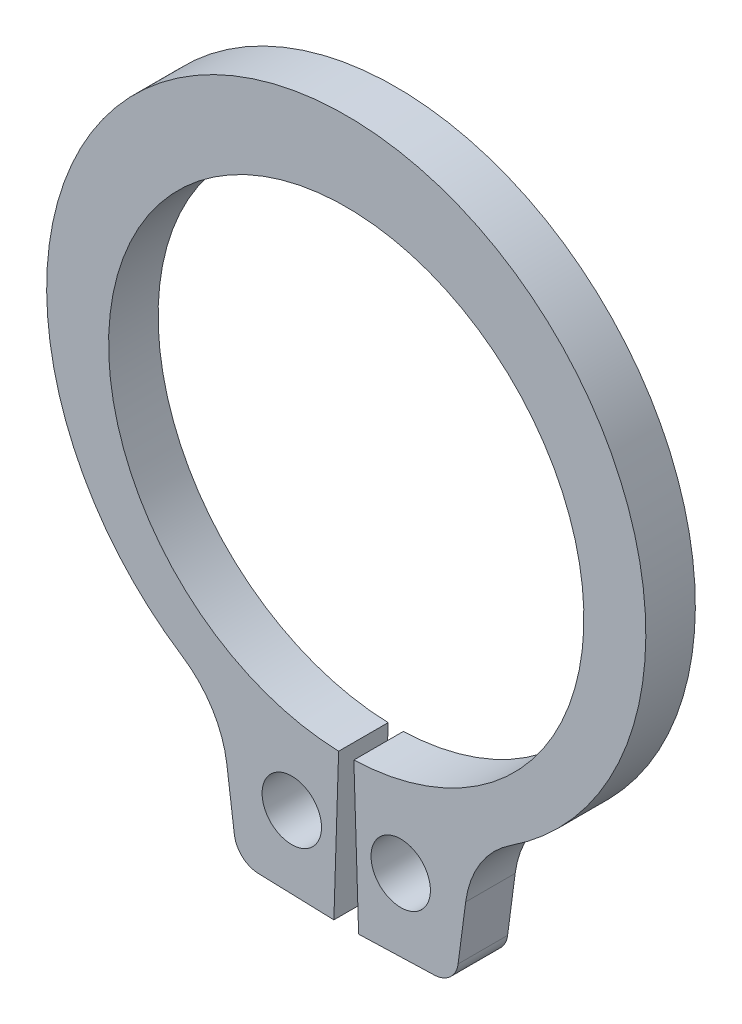
SolidWorks part; units mm, degrees
ref_plane "Plane1" through (0, 0, 0) normal (0, 0, 1) x (1, 0, 0)
ref_plane "Plane2" through (0, 0, 0) normal (0, 1, 0) x (1, 0, 0)
ref_plane "Plane3" through (0, 0, 0) normal (1, 0, 0) x (0, 0, -1)
sketch "Clipboard" plane through (0, 0, 0) normal (0, 0, 1) x (1, 0, 0)
  line L0 (0, 0) -> (1.6, 0)
  line L1 (0, 0) -> (0, 0.96)
  line L2 (0, 0) -> (0, -3)
  circle A0 centre (0, 0) radius 0.6
  circle A1 centre (0, 0) radius 5
  dimension "HoleDia" = 1.2
sketch "BodySke" plane through (0, 0, 0) normal (0, 0, 1) x (1, 0, 0)
  line L0 (-1.5431, 0) -> (1.5431, 0) construction
  line L1 (0, 0) -> (0, 6.4) construction
  line L2 (0.1538, -4.7975) -> (0.25, -7.796)
  line L3 (-0.1538, -4.7975) -> (-0.25, -7.796)
  line L4 (0, 0) -> (4.4335, -6.4174) construction
  line L5 (0, 0) -> (-4.4335, -6.4174) construction
  line L6 (0.25, -7.796) -> (1.7792, -7.747)
  line L7 (2.4118, -6.1513) -> (2.2589, -7.3125)
  line L8 (-2.4118, -6.1513) -> (-2.2589, -7.3125)
  line L9 (-0.25, -7.796) -> (-1.7792, -7.747)
  circle A0 centre (0, 0) radius 4.8 construction
  arc A1 (0.1538, -4.7975) -> (-0.1538, -4.7975) centre (0, 0) ccw
  arc A2 (3.274, -4.739) -> (-3.274, -4.739) centre (0, 0.3493) ccw construction
  arc A3 (0.25, -7.796) -> (1.9533, -7.5515) centre (0, 0) ccw construction
  arc A4 (3.316, -4.7118) -> (2.4118, -6.1513) centre (4.4335, -6.4174) ccw
  arc A5 (-2.4118, -6.1513) -> (-3.316, -4.7118) centre (-4.4335, -6.4174) ccw
  arc A6 (-1.9533, -7.5515) -> (-0.25, -7.796) centre (0, 0) ccw construction
  arc A7 (3.316, -4.7118) -> (-3.316, -4.7118) centre (0, 0.3493) ccw
  arc A8 (-2.4429, -5.9154) -> (2.4429, -5.9154) centre (0, 0) ccw construction
  circle A9 centre (1.1, -6.3048) radius 0.6
  circle A10 centre (-1.1, -6.3048) radius 0.6
  arc A11 (2.2589, -7.3125) -> (1.7792, -7.747) centre (1.7632, -7.2472) cw
  arc A12 (-2.2589, -7.3125) -> (-1.7792, -7.747) centre (-1.7632, -7.2472) ccw
  point P28 (2.2379, -7.4721)
  point P31 (-2.2379, -7.4721)
  dimension "HoleDia" = 1.2
  dimension "D3" = 0.5
  dimension "D2" = 15
  dimension "Gap" = 0.5
extrude "Body" add sketch "BodySke" against normal blind 1
equation "' \"ShaftDia@Clipboard\" = 10"
equation "' \"Thickness@Body\" = 1"
equation "' \"GrooveDia@BodySke\" = 9.6"
equation "' \"LugSection@Clipboard\" = 3.0"
equation "' \"LargeSection@Clipboard\" = 1.6"
equation "' \"HoleDia@Clipboard\" = 1.2"
equation "\"SmallSection@Clipboard\" =  \"LargeSection@Clipboard\" * 0.6"
equation "\"Gap@BodySke\" =  \"Thickness@Body\" / 2"
equation "\"LargeRad@BodySke\" =  \"GrooveDia@BodySke\" / 2 +  \"LargeSection@Clipboard\""
equation "\"SmallRad@BodySke\" =  \"GrooveDia@BodySke\" / 2 +  \"SmallSection@Clipboard\""
equation "\"LugRad@BodySke\" = \"GrooveDia@BodySke\" / 2 + \"LugSection@Clipboard\""
equation "\"HoleOffsetRad@BodySke\" = (  \"ShaftDia@Clipboard\" / 2 + \"LugRad@BodySke\" ) / 2"
equation "\"HoleSpacing@BodySke\" = \"Gap@BodySke\"  * 2 +  \"HoleDia@Clipboard\""
equation "\"HoleDia@BodySke\" =  \"HoleDia@Clipboard\""
equation "\"SmallAngle@BodySke\" = atn(\"HoleSpacing@BodySke\" / 2 / sqr(\"HoleOffsetRad@BodySke\"  * \"HoleOffsetRad@BodySke\" - (\"HoleSpacing@BodySke\" / 2) * (\"HoleSpacing@BodySke\" / 2) ))  * 7 * ( 180 / 3.141593)"
